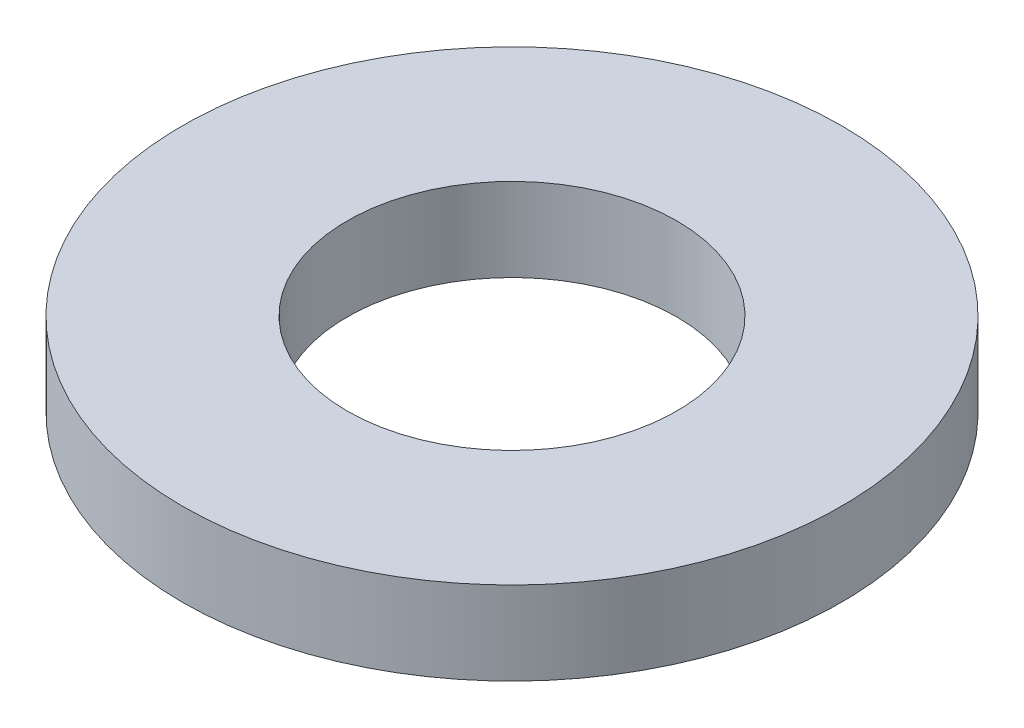
SolidWorks part; units mm, degrees
ref_plane "Front Plane" through (0, 0, 0) normal (0, 0, 1) x (1, 0, 0)
ref_plane "Top Plane" through (0, 0, 0) normal (0, 1, 0) x (1, 0, 0)
ref_plane "Right Plane" through (0, 0, 0) normal (1, 0, 0) x (0, 0, -1)
sketch "Sketch1" plane through (0, 0, 0) normal (0, 1, 0) x (1, 0, 0)
  circle A0 centre (0, 0) radius 95
  dimension "FLANGE_OD" = 190
extrude "Boss-Extrude1" add sketch "Sketch1" along normal blind 24
sketch "Sketch2" plane through (0, 0, 0) normal (0, 1, 0) x (1, 0, 0)
  circle A0 centre (0, 0) radius 47.5
  dimension "BORE_D" = 95
extrude "Cut-Extrude1" cut sketch "Sketch2" along normal through all
sketch "Sketch3" plane through (0, 24, 0) normal (0, 1, 0) x (1, 0, 0)
  circle A0 centre (0, 0) radius 27.3893 construction
  circle A1 centre (-27.3893, 0) radius 5.3377
  dimension "BOLT_D" = 10.6754
  dimension "BOLT_PCD" = 54.7787
extrude "Cut-Extrude2" cut sketch "Sketch3" against normal blind 16.1321 rebuild error yes
pattern_circular "CirPattern1" count 6 over 360 rebuild error yes
